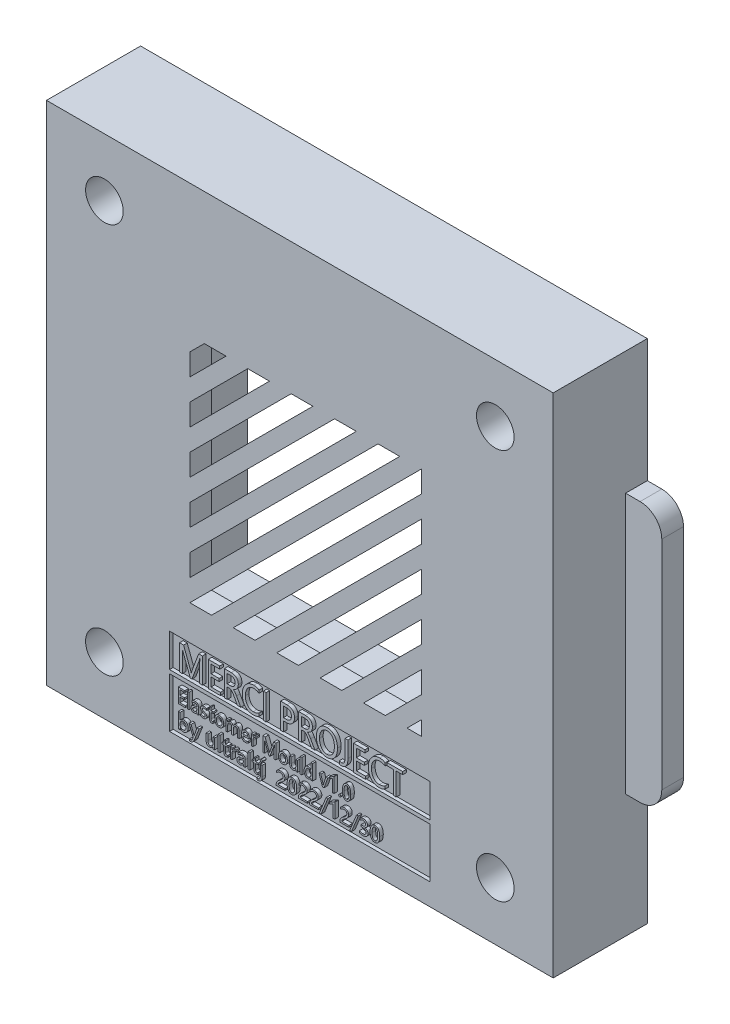
SolidWorks part; units mm, degrees
ref_plane "前视基准面" through (0, 0, 0) normal (0, 0, 1) x (1, 0, 0)
ref_plane "上视基准面" through (0, 0, 0) normal (0, 1, 0) x (1, 0, 0)
ref_plane "右视基准面" through (0, 0, 0) normal (1, 0, 0) x (0, 0, -1)
sketch "草图1" plane through (0, 0, 0) normal (0, 0, 1) x (1, 0, 0)
  line L1 (0, 0) -> (70, 0)
  line L2 (0, 0) -> (0, 70)
  line L3 (0, 70) -> (70, 70)
  line L4 (70, 0) -> (70, 70)
  dimension "D1" = 70
extrude "凸台-拉伸1" add sketch "草图1" along normal blind 13
sketch "草图2" plane through (0, 0, 0) normal (0, 0, 1) x (1, 0, 0)
  line L0 (70, 70) -> (0, 70) construction
  line L1 (35, 70) -> (35, 0) construction
  line L2 (0, 0) -> (70, 0) construction
  line L3 (0, 35) -> (70, 35) construction
  line L4 (0, 70) -> (0, 0) construction
  line L5 (70, 0) -> (70, 70) construction
  line L7 (14.8, 55.2) -> (55.2, 55.2)
  line L8 (14.8, 55.2) -> (14.8, 14.8)
  line L9 (14.8, 14.8) -> (55.2, 14.8)
  line L10 (55.2, 55.2) -> (55.2, 14.8)
  point P16 (35, 55.2)
  point P17 (14.8, 35)
  dimension "D1" = 40.4
extrude "切除-拉伸1" cut sketch "草图2" along normal blind 10
sketch "草图3" plane through (0, 0, 13) normal (0, 0, 1) x (1, 0, 0)
  line L0 (0, 35) -> (70, 35) construction
  line L1 (0, 70) -> (0, 0) construction
  line L2 (70, 0) -> (70, 70) construction
  line L3 (35, 70) -> (35, 0) construction
  line L4 (70, 70) -> (0, 70) construction
  line L5 (0, 0) -> (70, 0) construction
  line L6 (8, 62) -> (0, 62) construction
  line L7 (8, 62) -> (8, 70) construction
  circle A0 centre (8, 62) radius 2.6
  circle A1 centre (62, 62) radius 2.6
  circle A2 centre (62, 8) radius 2.6
  circle A3 centre (8, 8) radius 2.6
  point P12 (0, 35)
  point P13 (35, 70)
  dimension "D2" = 5.2
  dimension "D1" = 8
extrude "切除-拉伸2" cut sketch "草图3" against normal through all
sketch "草图4" plane through (0, 0, 10) normal (0, 0, -1) x (-1, 0, 0)
  line L0 (-56.8, 56.8) -> (-14.8, 14.8) construction
  line L1 (-56.8, 56.8) -> (-14.8, 56.8) construction
  line L2 (-56.8, 56.8) -> (-56.8, 14.8) construction
  line L3 (-56.8, 14.8) -> (-14.8, 14.8) construction
  line L4 (-14.8, 56.8) -> (-14.8, 14.8) construction
  line L5 (-53.8, 56.8) -> (-11.8, 14.8) construction
  line L6 (-51.8, 51.8) -> (-19.8, 51.8) construction
  line L7 (-51.8, 51.8) -> (-51.8, 19.8) construction
  line L8 (-51.8, 19.8) -> (-19.8, 19.8) construction
  line L9 (-19.8, 51.8) -> (-19.8, 19.8) construction
  line L10 (-46.8, 46.8) -> (-24.8, 46.8) construction
  line L11 (-46.8, 46.8) -> (-46.8, 24.8) construction
  line L12 (-46.8, 24.8) -> (-24.8, 24.8) construction
  line L13 (-24.8, 46.8) -> (-24.8, 24.8) construction
  line L14 (-41.8, 41.8) -> (-29.8, 41.8) construction
  line L15 (-41.8, 41.8) -> (-41.8, 29.8) construction
  line L16 (-41.8, 29.8) -> (-29.8, 29.8) construction
  line L17 (-29.8, 41.8) -> (-29.8, 29.8) construction
  line L18 (-50.8, 56.8) -> (-8.8, 14.8) construction
  line L19 (-47.8, 56.8) -> (-5.8, 14.8) construction
  line L20 (-44.8, 56.8) -> (-2.8, 14.8) construction
  line L21 (-41.8, 56.8) -> (0.2, 14.8) construction
  line L22 (-38.8, 56.8) -> (3.2, 14.8) construction
  line L23 (-35.8, 56.8) -> (6.2, 14.8) construction
  line L24 (-32.8, 56.8) -> (9.2, 14.8) construction
  line L25 (-29.8, 56.8) -> (12.2, 14.8) construction
  line L26 (-26.8, 56.8) -> (15.2, 14.8) construction
  line L27 (-23.8, 56.8) -> (18.2, 14.8) construction
  line L28 (-20.8, 56.8) -> (21.2, 14.8) construction
  line L29 (-17.8, 56.8) -> (24.2, 14.8) construction
  line L30 (-59.8, 56.8) -> (-17.8, 14.8) construction
  line L31 (-62.8, 56.8) -> (-20.8, 14.8) construction
  line L32 (-65.8, 56.8) -> (-23.8, 14.8) construction
  line L33 (-68.8, 56.8) -> (-26.8, 14.8) construction
  line L34 (-71.8, 56.8) -> (-29.8, 14.8) construction
  line L35 (-74.8, 56.8) -> (-32.8, 14.8) construction
  line L36 (-77.8, 56.8) -> (-35.8, 14.8) construction
  line L37 (-80.8, 56.8) -> (-38.8, 14.8) construction
  line L38 (-83.8, 56.8) -> (-41.8, 14.8) construction
  line L39 (-86.8, 56.8) -> (-44.8, 14.8) construction
  line L40 (-89.8, 56.8) -> (-47.8, 14.8) construction
  line L41 (-92.8, 56.8) -> (-50.8, 14.8) construction
  line L42 (-95.8, 56.8) -> (-53.8, 14.8) construction
  line L43 (-51.8, 51.8) -> (-51.8, 48.8)
  line L44 (-51.8, 48.8) -> (-22.8, 19.8)
  line L45 (-22.8, 19.8) -> (-19.8, 19.8)
  line L46 (-19.8, 19.8) -> (-51.8, 51.8)
  line L47 (-48.8, 51.8) -> (-19.8, 22.8)
  line L48 (-19.8, 22.8) -> (-19.8, 25.8)
  line L49 (-19.8, 25.8) -> (-45.8, 51.8)
  line L50 (-45.8, 51.8) -> (-48.8, 51.8)
  line L51 (-42.8, 51.8) -> (-19.8, 28.8)
  line L52 (-19.8, 28.8) -> (-19.8, 31.8)
  line L53 (-19.8, 31.8) -> (-39.8, 51.8)
  line L54 (-39.8, 51.8) -> (-42.8, 51.8)
  line L55 (-36.8, 51.8) -> (-19.8, 34.8)
  line L56 (-19.8, 34.8) -> (-19.8, 37.8)
  line L57 (-19.8, 37.8) -> (-33.8, 51.8)
  line L58 (-33.8, 51.8) -> (-36.8, 51.8)
  line L59 (-30.8, 51.8) -> (-19.8, 40.8)
  line L60 (-19.8, 40.8) -> (-19.8, 43.8)
  line L61 (-19.8, 43.8) -> (-27.8, 51.8)
  line L62 (-27.8, 51.8) -> (-30.8, 51.8)
  line L63 (-24.8, 51.8) -> (-19.8, 46.8)
  line L64 (-19.8, 46.8) -> (-19.8, 49.8)
  line L65 (-19.8, 49.8) -> (-21.8, 51.8)
  line L66 (-21.8, 51.8) -> (-24.8, 51.8)
  line L67 (-51.8, 45.8) -> (-51.8, 42.8)
  line L68 (-51.8, 42.8) -> (-28.8, 19.8)
  line L69 (-28.8, 19.8) -> (-25.8, 19.8)
  line L70 (-25.8, 19.8) -> (-51.8, 45.8)
  line L71 (-51.8, 39.8) -> (-31.8, 19.8)
  line L72 (-31.8, 19.8) -> (-34.8, 19.8)
  line L73 (-34.8, 19.8) -> (-51.8, 36.8)
  line L74 (-51.8, 36.8) -> (-51.8, 39.8)
  line L75 (-51.8, 33.8) -> (-37.8, 19.8)
  line L76 (-37.8, 19.8) -> (-40.8, 19.8)
  line L77 (-40.8, 19.8) -> (-51.8, 30.8)
  line L78 (-51.8, 30.8) -> (-51.8, 33.8)
  line L79 (-51.8, 27.8) -> (-51.8, 24.8)
  line L80 (-51.8, 24.8) -> (-46.8, 19.8)
  line L81 (-46.8, 19.8) -> (-43.8, 19.8)
  line L82 (-43.8, 19.8) -> (-51.8, 27.8)
  line L83 (-51.8, 21.8) -> (-49.8, 19.8)
  line L84 (-49.8, 19.8) -> (-51.8, 19.8)
  line L85 (-51.8, 19.8) -> (-51.8, 21.8)
  dimension "D1" = 5
  dimension "D2" = 5
  dimension "D3" = 5
  dimension "D4" = 5
  dimension "D5" = 5
  dimension "D6" = 5
  dimension "D7" = 14
  dimension "D8" = 14
extrude "切除-拉伸3" cut sketch "草图4" against normal through all
sketch "草图5" plane through (0, 0, 0) normal (0, 0, -1) x (-1, 0, 0)
  line L0 (0, 35) -> (-70, 35) construction
  line L1 (0, 70) -> (-70, 70) construction
  line L2 (0, 70) -> (0, 0) construction
  line L3 (0, 0) -> (-70, 0) construction
  line L4 (-70, 70) -> (-70, 0) construction
  line L5 (-35, 70) -> (-35, 0) construction
  line L6 (-70, 17) -> (-72, 17)
  line L7 (0, 53) -> (2, 53)
  line L8 (0, 53) -> (0, 17)
  line L9 (0, 17) -> (2, 17)
  line L10 (5, 50) -> (5, 20)
  line L11 (-75, 50) -> (-75, 20)
  line L12 (-70, 53) -> (-72, 53)
  line L13 (-70, 53) -> (-70, 17)
  arc A0 (2, 17) -> (5, 20) centre (2, 20) ccw
  arc A1 (2, 53) -> (5, 50) centre (2, 50) cw
  arc A2 (-72, 17) -> (-75, 20) centre (-72, 20) cw
  arc A3 (-72, 53) -> (-75, 50) centre (-72, 50) ccw
  point P7 (0, 35)
  point P15 (5, 35)
  point P18 (5, 17)
  point P21 (5, 53)
  dimension "D3" = 3
  dimension "D1" = 5
  dimension "D2" = 36
extrude "凸台-拉伸2" add sketch "草图5" against normal blind 3
sketch "草图6" plane through (0, 0, 13) normal (0, 0, 1) x (1, 0, 0)
  line L1 (17, 15) -> (53, 15)
  line L2 (17, 15) -> (17, 3)
  line L3 (17, 3) -> (53, 3)
  line L4 (53, 15) -> (53, 3)
  line L5 (0, 0) -> (70, 0) construction
  line L6 (35, 70) -> (35, 0) construction
  line L7 (70, 70) -> (0, 70) construction
  point P10 (35, 15)
  dimension "D1" = 12
  dimension "D2" = 3
  dimension "D3" = 36
extrude "切除-拉伸4" cut sketch "草图6" against normal blind 0.5
sketch "草图7" plane through (0, 0, 12.5) normal (0, 0, 1) x (1, 0, 0)
  line L0 (18, 14.5229) -> (18, 11.5546) construction
  line L1 (17, 15) -> (17, 3) construction
  line L2 (53, 3) -> (53, 15) construction
  line L3 (17, 10.4) -> (53, 10.4)
  line L4 (17, 10.4) -> (17, 9.9)
  line L5 (17, 9.9) -> (53, 9.9)
  line L6 (53, 10.4) -> (53, 9.9)
  line L7 (53, 15) -> (17, 15) construction
  text T0 "MERCI PROJECT" font "微软雅黑" height 3.5
  text T1 "Elastomer Mould v1.0\r\n" font "微软雅黑" height 2
  text T2 "by ultraltj  2022/12/30" font "微软雅黑" height 2
  dimension "D1" = 1
  dimension "D2" = 0.5
  dimension "D3" = 0.4
  dimension "D4" = 4.6
extrude "凸台-拉伸3" add sketch "草图7" along normal blind 0.5
